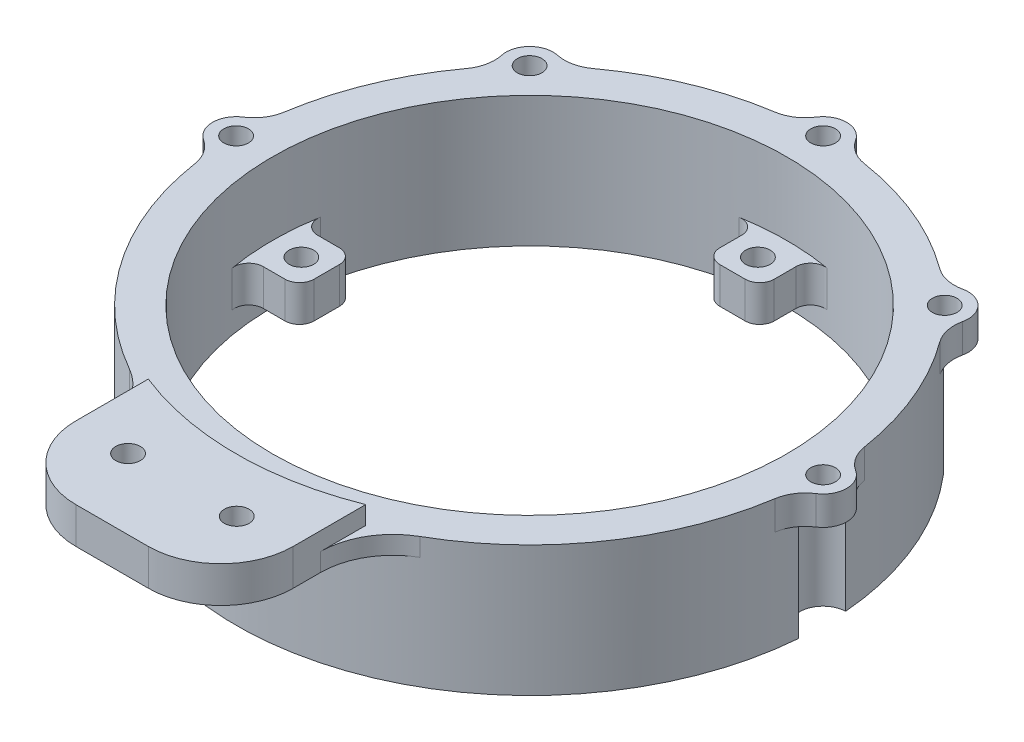
SolidWorks part; units mm, degrees
ref_plane "Alzado" through (0, 0, 0) normal (0, 0, 1) x (1, 0, 0)
ref_plane "Planta" through (0, 0, 0) normal (0, 1, 0) x (1, 0, 0)
ref_plane "Vista lateral" through (0, 0, 0) normal (1, 0, 0) x (0, 0, -1)
sketch "Croquis1" plane through (0, 0, 0) normal (0, 1, 0) x (1, 0, 0)
  circle A0 centre (0, 0) radius 35.5
  circle A1 centre (0, 0) radius 40.5
  dimension "D1" = 71
  dimension "D2" = 5
extrude "Saliente-Extruir1" add sketch "Croquis1" along normal mid plane 18
sketch "Croquis2" plane through (0, 9, 0) normal (0, -1, 0) x (1, 0, 0)
  line L0 (-15, 37.6198) -> (-15, 57.6198)
  line L1 (-15, 57.6198) -> (15, 57.6198)
  line L2 (15, 57.6198) -> (15, 37.6198)
  line L3 (0, 0) -> (0, 98.2113) construction
  circle A0 centre (0, 0) radius 40.5 construction
  arc A1 (15, 37.6198) -> (-15, 37.6198) centre (0, 0) ccw
  circle A2 centre (-7.5, 47.9166) radius 1.7
  circle A3 centre (7.5, 47.9166) radius 1.7
  circle A6 centre (0, 0) radius 48.5
  circle A7 centre (0, 0) radius 48.5 construction
  point P7 (0, 57.6198)
  dimension "D5" = 3.4
  dimension "D1" = 30
  dimension "D2" = 20
  dimension "D3" = 8
  dimension "D4" = 15
extrude "Saliente-Extruir2" add sketch "Croquis2" along normal mid plane 5
fillet "Redondeo1" radius 10 4 edges at (15, 7.75, 37.6198) (-15, 7.75, 37.6198) (-15, 9, 57.6198) (15, 9, 57.6198)
ref_plane "Plano1" through (0, -6, 0) normal (0, -1, 0) x (-1, 0, 0)
sketch "Croquis4" plane through (0, -6, 0) normal (0, -1, 0) x (-1, 0, 0)
  line L0 (0, -35.5) -> (0, 0) construction
  line L1 (-3.75, -35.3014) -> (-3.75, -28)
  line L2 (-3.75, -28) -> (3.75, -28)
  line L3 (3.75, -35.3014) -> (3.75, -28)
  circle A0 centre (0, 0) radius 35.5 construction
  arc A1 (-3.75, -35.3014) -> (3.75, -35.3014) centre (0, 0) ccw
  circle A2 centre (0, 0) radius 25 construction
  circle A3 centre (0, -31.5) radius 1.7
  circle A4 centre (0, 0) radius 31.5 construction
  point P12 (0, -28)
  dimension "D1" = 3.4
  dimension "D5" = 50
  dimension "D6" = 6.5
  dimension "D3" = 7.5
  dimension "D4" = 3.75
extrude "Saliente-Extruir3" add sketch "Croquis4" against normal blind 5
fillet "Redondeo2" radius 2 4 edges at (-3.75, -3.5, 35.3014) (3.75, -3.5, 28) (-3.75, -3.5, 28) (3.75, -3.5, 35.3014)
pattern_circular "MatrizC1" count 4 every 90 about axis through (0, 9, 0) along (0, 1, 0) of "Saliente-Extruir3", "Redondeo2"
hole_wizard "Refrentado para tornillo con cabeza plana de M31" positions "Croquis5" profile "Croquis7" counterbore size "M3" standard "ISO" end condition through all
sketch "Croquis5" plane through (0, -9, 0) normal (0, -1, 0) x (-1, 0, 0)
  circle A0 centre (0, 0) radius 40.5 construction
  point P0 (0, 40.5)
sketch "Croquis7" plane through (0, -9, -40.5) normal (1, 0, 0) x (0, 0, -1)
  line L0 (0, 0) -> (0, 20.5)
  line L1 (0, 20.5) -> (1.7, 20.5)
  line L3 (1.7, 20.5) -> (1.7, 14)
  line L4 (1.7, 14) -> (3.25, 14)
  line L5 (3.25, 14) -> (3.25, 0)
  line L7 (3.25, 0) -> (0, 0)
  line L11 (0, -6.35) -> (0, 107.95) construction
  dimension "Diámetro de taladro hasta el siguiente" = 3.4
  dimension "Profundidad de taladro hasta el siguiente" = 20.5
  dimension "Diámetro de refrentado" = 6.5
  dimension "Profundidad de refrentado" = 14
sketch "Croquis8" plane through (0, 5, 0) normal (0, -1, 0) x (1, 0, 0)
  circle A0 centre (0, -40.5) radius 3.25
  circle A2 centre (0, -40.5) radius 1.7
extrude "Saliente-Extruir4" add sketch "Croquis8" against normal up to surface (4 mm away) up to face at (0, 9, 17.7263)
pattern_circular "MatrizC2" count 3 every 45 about axis through (0, -9, 0) along (0, 1, 0) of "Saliente-Extruir4", "Refrentado para tornillo con cabeza plana de M31"
mirror "Simetría1" about plane through (0, 0, 0) normal (1, 0, 0) of "MatrizC2"
fillet "Redondeo4" radius 5 10 edges at (-40.3696, 7, -3.2474) (-40.3696, 7, 3.2474) (-30.8419, 7, -26.2494) (-26.2494, 7, -30.8419) (-3.2474, 7, -40.3696) (3.2474, 7, -40.3696) (40.3696, 7, -3.2474) (40.3696, 7, 3.2474) (30.8419, 7, -26.2494) (26.2494, 7, -30.8419)
